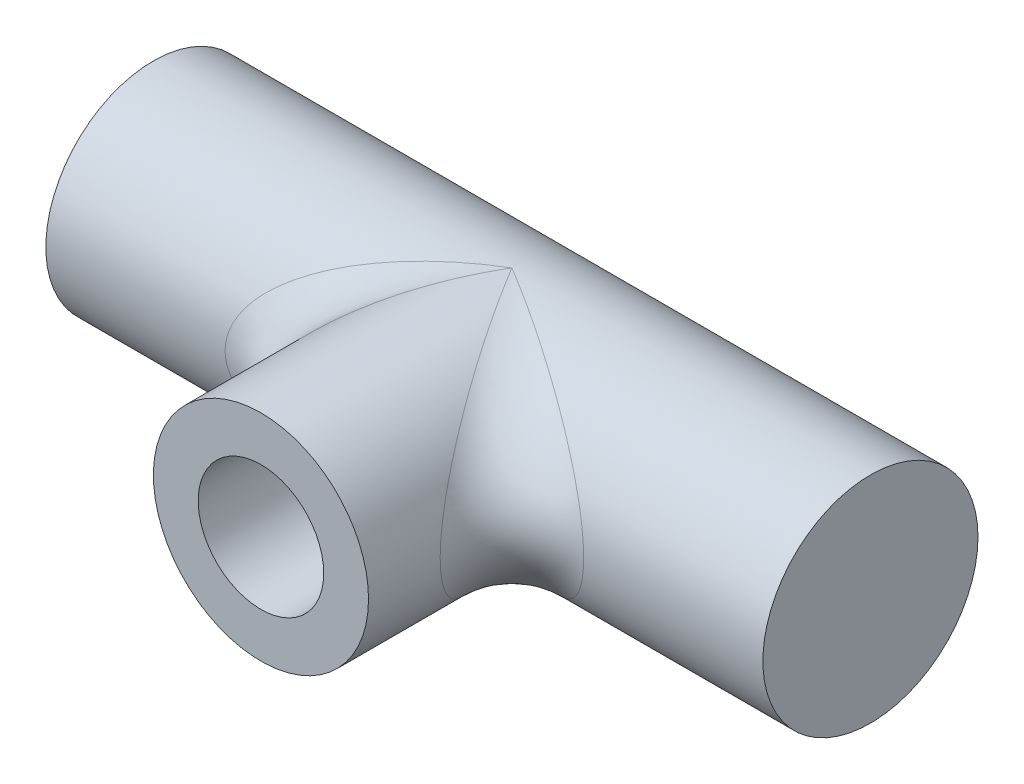
SolidWorks part; units mm, degrees
ref_plane "Front Plane" through (0, 0, 0) normal (0, 0, 1) x (1, 0, 0)
ref_plane "Top Plane" through (0, 0, 0) normal (0, 1, 0) x (1, 0, 0)
ref_plane "Right Plane" through (0, 0, 0) normal (1, 0, 0) x (0, 0, -1)
sketch "Sketch1" plane through (0, 0, 0) normal (1, 0, 0) x (0, 0, -1)
  circle A0 centre (0, 0) radius 3.81
  dimension "D1" = 7.62
extrude "Boss-Extrude1" add sketch "Sketch1" along normal blind 25.4
sketch "Sketch3" plane through (0, 0, 0) normal (0, 0, 1) x (1, 0, 0)
  line L0 (12.6999, 2.7761) -> (12.6999, -3.1529)
  line L1 (0, 0) -> (25.4, 0) construction
  line L2 (25.4, -3.81) -> (25.4, 3.81) construction
  circle A1 centre (12.7, 0) radius 3.81
  dimension "D2" = 7.62
extrude "Boss-Extrude2" add sketch "Sketch3" along normal blind 8.89
sketch "Sketch5" plane through (0, 0, 8.89) normal (0, 0, 1) x (1, 0, 0)
  circle A0 centre (12.7, 0) radius 2.2225
  circle A1 centre (12.7, 0) radius 3.81 construction
  dimension "D1" = 4.445
extrude "Cut-Extrude1" cut sketch "Sketch5" against normal blind 6.35
fillet "Fillet1" radius 2.54 2 edges at (16.51, 0, 3.81) (8.89, 0, 3.81)
